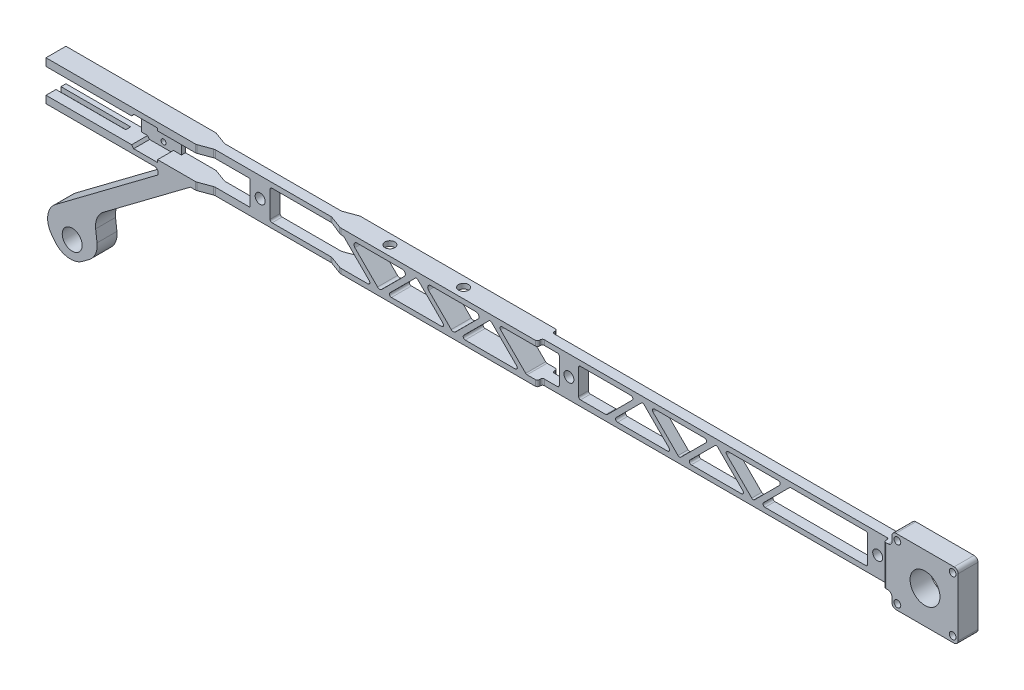
SolidWorks part; units mm, degrees
material "Magnesium Alloy"
ref_plane "Front Plane" through (0, 0, 0) normal (0, 0, 1) x (1, 0, 0)
ref_plane "Top Plane" through (0, 0, 0) normal (0, 1, 0) x (1, 0, 0)
ref_plane "Right Plane" through (0, 0, 0) normal (1, 0, 0) x (0, 0, -1)
sketch "Sketch1" plane through (0, 0, 0) normal (0, 0, 1) x (1, 0, 0)
  line L0 (2.54, 0) -> (568.96, 0)
  line L1 (571.5, 2.54) -> (571.5, 22.86)
  line L2 (568.96, 25.4) -> (2.54, 25.4)
  line L3 (0, 22.86) -> (0, 2.54)
  line L4 (0, 22.86) -> (0, 25.4)
  line L5 (0, 25.4) -> (2.54, 25.4)
  line L6 (2.54, 0) -> (0, 0)
  line L7 (0, 0) -> (0, 2.54)
  arc A1 (568.96, 25.4) -> (571.5, 22.86) centre (568.96, 22.86) cw
  arc A2 (571.5, 2.54) -> (568.96, 0) centre (568.96, 2.54) cw
  point P7 (0, 25.4)
  point P12 (571.5, 0)
  point P15 (0, 0)
  dimension "D1" = 571.5
  dimension "D2" = 25.4
extrude "Boss-Extrude1" add sketch "Sketch1" along normal blind 12.7
sketch "Sketch2" plane through (0, 0, 0) normal (0, 0, 1) x (1, 0, 0)
  line L0 (173.2461, 3.175) -> (205.2139, 3.175)
  line L1 (206.112, 5.343) -> (190.128, 21.327)
  line L2 (188.332, 21.327) -> (172.348, 5.343)
  line L3 (0, 0) -> (568.96, 0) construction
  line L4 (0, 25.4) -> (0, 0) construction
  arc A0 (188.332, 21.327) -> (190.128, 21.327) centre (189.23, 20.4289) cw
  arc A1 (206.112, 5.343) -> (205.2139, 3.175) centre (205.2139, 4.445) cw
  arc A2 (173.2461, 3.175) -> (172.348, 5.343) centre (173.2461, 4.445) cw
  point P9 (189.23, 22.225)
  point P12 (208.28, 3.175)
  point P15 (170.18, 3.175)
  dimension "D5" = 1.27
  dimension "D1" = 38.1
  dimension "D2" = 19.05
  dimension "D3" = 3.175
  dimension "D4" = 170.18
extrude "Cut-Extrude1" cut sketch "Sketch2" along normal blind 12.7
pattern_linear "LPattern1" count 7 spacing 46.99 along (1, 0, 0) skipping (1, 0), (2, 0), (3, 0) of "Cut-Extrude1"
sketch "Sketch3" plane through (0, 0, 0) normal (0, 0, 1) x (1, 0, 0)
  line L0 (149.7511, 22.225) -> (181.7189, 22.225)
  line L1 (182.617, 20.057) -> (166.633, 4.073)
  line L2 (164.837, 4.073) -> (148.853, 20.057)
  line L3 (568.96, 25.4) -> (0, 25.4) construction
  line L4 (0, 25.4) -> (0, 0) construction
  arc A0 (164.837, 4.073) -> (166.633, 4.073) centre (165.735, 4.9711) ccw
  arc A1 (182.617, 20.057) -> (181.7189, 22.225) centre (181.7189, 20.955) ccw
  arc A2 (149.7511, 22.225) -> (148.853, 20.057) centre (149.7511, 20.955) ccw
  point P9 (165.735, 3.175)
  point P12 (184.785, 22.225)
  point P15 (146.685, 22.225)
  dimension "D5" = 1.27
  dimension "D1" = 38.1
  dimension "D2" = 19.05
  dimension "D3" = 3.175
  dimension "D4" = 146.685
extrude "Cut-Extrude2" cut sketch "Sketch3" along normal blind 12.7
pattern_linear "LPattern2" count 8 spacing 46.99 along (1, 0, 0) skipping (1, 0), (2, 0) of "Cut-Extrude2"
ref_plane "Plane1" through (279.4, 0, 0) normal (1, 0, 0) x (0, 0, -1)
ref_plane "Plane2" through (330.2, 0, 0) normal (1, 0, 0) x (0, 0, -1)
sketch "Sketch37" plane through (0, 0, 12.7) normal (0, 0, 1) x (1, 0, 0)
  line L0 (198.2741, 22.225) -> (227.1759, 22.225)
  line L1 (228.523, 18.973) -> (214.072, 4.522)
  line L2 (211.378, 4.522) -> (196.927, 18.973)
  line L3 (0, 25.4) -> (0, 0) construction
  line L4 (568.96, 25.4) -> (0, 25.4) construction
  line L5 (206.112, 5.343) -> (190.128, 21.327) construction
  arc A0 (214.072, 4.522) -> (211.378, 4.522) centre (212.725, 5.8691) cw
  arc A1 (228.523, 18.973) -> (227.1759, 22.225) centre (227.1759, 20.32) ccw
  arc A2 (198.2741, 22.225) -> (196.927, 18.973) centre (198.2741, 20.32) ccw
  point P14 (231.775, 22.225)
  point P17 (193.675, 22.225)
  dimension "D4" = 1.905
  dimension "D1" = 38.1
  dimension "D2" = 193.675
  dimension "D3" = 3.175
extrude "Cut-Extrude13" cut sketch "Sketch37" against normal up to surface (12.7 mm away) up to face at (380.3287, 12.7, 0)
pattern_linear "LPattern5" count 2 spacing 46.99 along (1, 0, 0) of "Cut-Extrude13"
sketch "Sketch34" plane through (0, 0, 12.7) normal (0, 0, 1) x (1, 0, 0)
  line L0 (220.2361, 3.175) -> (252.2039, 3.175)
  line L1 (253.102, 5.343) -> (237.118, 21.327)
  line L2 (235.322, 21.327) -> (219.338, 5.343)
  line L3 (0, 0) -> (568.96, 0) construction
  line L4 (0, 25.4) -> (0, 0) construction
  line L6 (214.072, 4.522) -> (228.523, 18.973) construction
  arc A0 (235.322, 21.327) -> (237.118, 21.327) centre (236.22, 20.4289) cw
  arc A1 (253.102, 5.343) -> (252.2039, 3.175) centre (252.2039, 4.445) cw
  arc A2 (219.338, 5.343) -> (220.2361, 3.175) centre (220.2361, 4.445) ccw
  point P13 (255.27, 3.175)
  point P16 (217.17, 3.175)
  dimension "D4" = 1.27
  dimension "D1" = 38.1
  dimension "D2" = 3.175
  dimension "D3" = 217.17
extrude "Cut-Extrude10" cut sketch "Sketch34" against normal up to surface (12.7 mm away) up to face at (259.715, 15.297, 0)
pattern_linear "LPattern3" count 2 spacing 46.99 along (1, 0, 0) of "Cut-Extrude10"
sketch "Sketch19" plane through (0, 0, 0) normal (-1, 0, 0) x (0, 0, 1)
  line L0 (3.175, 1.5875) -> (6.35, 1.5875)
  line L1 (6.35, 1.5875) -> (6.35, 23.8125)
  line L2 (6.35, 23.8125) -> (3.175, 23.8125)
  line L3 (3.175, 23.8125) -> (3.175, 1.5875)
  line L4 (0, 25.4) -> (0, 0) construction
  line L5 (12.7, 0) -> (0, 0) construction
  dimension "D1" = 3.175
  dimension "D2" = 3.175
  dimension "D3" = 22.225
  dimension "D4" = 1.5875
extrude "Cut-Extrude4" cut sketch "Sketch19" against normal blind 44.45
sketch "Sketch18" plane through (0, 0, 12.7) normal (0, 0, 1) x (1, 0, 0)
  line L0 (0, 20.574) -> (50.8, 20.574)
  line L1 (0, 25.4) -> (0, 0) construction
  line L2 (50.8, 20.574) -> (50.8, 4.699)
  line L3 (50.8, 4.699) -> (0, 4.699)
  line L4 (0, 4.699) -> (0, 20.574)
  line L5 (568.96, 25.4) -> (0, 25.4) construction
  dimension "D1" = 50.8
  dimension "D2" = 15.875
  dimension "D3" = 4.826
extrude "Cut-Extrude3" cut sketch "Sketch18" against normal through all
sketch "Sketch20" plane through (0, 0, 12.7) normal (0, 0, 1) x (1, 0, 0)
  line L0 (50.8, 20.574) -> (54.61, 20.574)
  line L1 (54.61, 20.574) -> (55.88, 22.1615)
  line L2 (55.88, 22.1615) -> (71.12, 22.1615)
  line L3 (71.12, 22.1615) -> (71.12, 20.574)
  line L4 (71.12, 20.574) -> (127, 20.574)
  line L5 (127, 20.574) -> (127, 4.699)
  line L6 (127, 4.699) -> (71.12, 4.699)
  line L7 (71.12, 4.699) -> (71.12, 3.1115)
  line L8 (71.12, 3.1115) -> (55.88, 3.1115)
  line L9 (55.88, 3.1115) -> (54.61, 4.699)
  line L10 (54.61, 4.699) -> (50.8, 4.699)
  line L11 (50.8, 4.699) -> (50.8, 20.574)
  dimension "D1" = 3.81
  dimension "D2" = 1.5875
  dimension "D3" = 15.24
  dimension "D4" = 16.51
  dimension "D5" = 76.2
extrude "Cut-Extrude5" cut sketch "Sketch20" against normal blind 10.16
sketch "Sketch21" plane through (0, 0, 2.54) normal (0, 0, 1) x (1, 0, 0)
  line L0 (127, 20.574) -> (127, 4.699)
  line L1 (127, 4.699) -> (76.2, 4.699)
  line L2 (71.12, 4.699) -> (127, 4.699) construction
  line L3 (76.2, 4.699) -> (76.2, 20.574)
  line L4 (127, 20.574) -> (71.12, 20.574) construction
  line L5 (76.2, 20.574) -> (127, 20.574)
  dimension "D1" = 50.8
extrude "Cut-Extrude6" cut sketch "Sketch21" against normal through all
hole_wizard "1/8 (0.125) Diameter Hole1" positions "Sketch22" profile "Sketch23" hole size "1/8" standard "ANSI Inch" end condition through all
sketch "Sketch22" plane through (0, 0, 2.54) normal (0, 0, 1) x (1, 0, 0)
  line L0 (76.2, 20.574) -> (76.2, 4.699) construction
  line L1 (55.88, 3.1115) -> (71.12, 3.1115) construction
  line L2 (71.12, 22.1615) -> (55.88, 22.1615) construction
  point P0 (64.77, 18.9865)
  point P2 (64.77, 6.2865)
  dimension "D1" = 11.43
  dimension "D2" = 11.43
  dimension "D3" = 3.175
  dimension "D4" = 3.175
sketch "Sketch23" plane through (64.77, 18.9865, 2.54) normal (1, 0, 0) x (0, -1, 0)
  line L0 (0, 0) -> (0, 2.54)
  line L1 (0, 2.54) -> (1.5875, 2.54)
  line L2 (1.5875, 2.54) -> (1.5875, 0)
  line L5 (1.5875, 0) -> (0, 0)
  line L11 (0, -6.35) -> (0, 107.95) construction
  dimension "Thru Hole Dia." = 3.175
  dimension "Thru Hole Depth" = 2.54
ref_axis "Axis1" through (189.23, 21.6989, 12.7) along (0, 0, -1)
sketch "Sketch46" plane through (0, 0, 12.7) normal (0, 0, 1) x (1, 0, 0)
  line L2 (173.2461, 3.175) -> (140.97, 3.175)
  line L4 (139.7, 20.955) -> (139.7, 4.445)
  line L5 (127, 4.699) -> (127, 20.574) construction
  line L7 (173.2461, 3.175) -> (189.23, 21.6989)
  line L8 (181.7189, 22.225) -> (189.23, 21.6989)
  line L9 (181.7189, 22.225) -> (140.97, 22.225)
  arc A0 (139.7, 4.445) -> (140.97, 3.175) centre (140.97, 4.445) ccw
  arc A1 (140.97, 22.225) -> (139.7, 20.955) centre (140.97, 20.955) ccw
  dimension "D1" = 1.27
  dimension "D2" = 12.7
extrude "Cut-Extrude17" cut sketch "Sketch46" against normal up to surface (12.7 mm away) up to face at (66.3575, 18.9865, 0)
sketch "Sketch35" plane through (0, 0, 12.7) normal (0, 0, 1) x (1, 0, 0)
  line L13 (198.2741, 22.225) -> (214.072, 4.522)
  line L14 (214.072, 4.522) -> (212.725, 3.175)
  line L15 (212.725, 3.175) -> (140.97, 3.175)
  line L16 (198.2741, 22.225) -> (140.97, 22.225)
  line L17 (139.7, 20.955) -> (139.7, 4.445)
  line L18 (214.072, 4.522) -> (228.523, 18.973) construction
  line L19 (140.97, 3.175) -> (205.2139, 3.175) construction
  line L20 (127, 4.699) -> (127, 20.574) construction
  arc A5 (139.7, 4.445) -> (140.97, 3.175) centre (140.97, 4.445) ccw
  arc A6 (140.97, 22.225) -> (139.7, 20.955) centre (140.97, 20.955) ccw
  dimension "D2" = 1.27
  dimension "D1" = 12.7
extrude "Cut-Extrude11" [suppressed] cut sketch "Sketch35" against normal up to surface (12.7 mm away)
sketch "Sketch36" plane through (0, 0, 12.7) normal (0, 0, 1) x (1, 0, 0)
  line L0 (306.705, 3.7011) -> (322.834, 3.7011)
  line L1 (324.104, 4.9711) -> (324.104, 20.955)
  line L2 (322.834, 22.225) -> (322.6889, 22.225)
  line L3 (322.6889, 22.225) -> (306.705, 3.7011)
  line L4 (330.2, -6.985) -> (330.2, 6.985) construction
  arc A0 (305.807, 4.073) -> (307.603, 4.073) centre (306.705, 4.9711) ccw construction
  arc A1 (324.104, 4.9711) -> (322.834, 3.7011) centre (322.834, 4.9711) cw
  arc A2 (324.104, 20.955) -> (322.834, 22.225) centre (322.834, 20.955) ccw
  dimension "D2" = 1.27
  dimension "D1" = 6.096
extrude "Cut-Extrude12" cut sketch "Sketch36" against normal up to surface (12.7 mm away) up to face at (171.5874, 14.6574, 0)
mirror "Mirror1" about plane through (330.2, 0, 0) normal (1, 0, 0) of "Cut-Extrude12"
sketch "Sketch45" plane through (0, 0, 12.7) normal (0, 0, 1) x (1, 0, 0)
  line L5 (487.1539, 3.175) -> (519.43, 3.175)
  line L7 (487.1539, 3.175) -> (470.272, 21.327)
  line L8 (470.272, 21.327) -> (470.798, 21.853)
  line L9 (471.6961, 22.225) -> (510.6489, 22.225)
  line L10 (470.272, 21.327) -> (454.288, 5.343) construction
  line L13 (520.7, 4.445) -> (520.7, 20.955)
  line L14 (519.43, 22.225) -> (510.6489, 22.225)
  line L15 (330.2, -6.985) -> (330.2, 6.985) construction
  arc A3 (471.6961, 22.225) -> (470.798, 21.853) centre (471.6961, 20.955) ccw
  arc A4 (519.43, 22.225) -> (520.7, 20.955) centre (519.43, 20.955) cw
  arc A5 (520.7, 4.445) -> (519.43, 3.175) centre (519.43, 4.445) cw
  dimension "D1" = 190.5
  dimension "D3" = 1.27
  dimension "D2" = 1.27
sketch "Sketch8" plane through (0, 0, 0) normal (0, 0, 1) x (1, 0, 0)
  line L0 (92.075, 0) -> (-9.525, -76.2)
  line L1 (0, 0) -> (568.96, 0) construction
  line L2 (-9.525, -76.2) -> (-15.24, -68.58)
  line L3 (-15.24, -68.58) -> (76.2, 0)
  line L4 (76.2, 0) -> (92.075, 0)
  line L6 (0, 25.4) -> (0, 20.574) construction
  dimension "D1" = 76.2
  dimension "D2" = 101.6
  dimension "D3" = 9.525
  dimension "D4" = 76.2
extrude "Boss-Extrude3" add sketch "Sketch8" along normal blind 12.7
sketch "Sketch13" plane through (0, 0, 0) normal (0, 0, 1) x (1, 0, 0)
  line L1 (76.2, 0) -> (-15.24, -68.58) construction
  line L5 (69.85, 0) -> (76.2, 0)
  line L6 (76.2, 0) -> (71.12, -3.81)
  arc A0 (69.85, 0) -> (71.12, -3.81) centre (69.0094, -2.3969) cw
  point P10 (76.2, 0)
  dimension "D1" = 2.54
  dimension "D2" = 6.35
extrude "Boss-Extrude4" add sketch "Sketch13" along normal blind 12.7
sketch "Sketch29" plane through (0, 0, 12.7) normal (0, 0, 1) x (1, 0, 0)
  line L0 (-9.525, -76.2) -> (1.651, -67.818)
  line L1 (-9.525, -76.2) -> (92.075, 0) construction
  line L2 (1.651, -67.818) -> (-0.254, -65.278)
  line L3 (-0.254, -65.278) -> (-11.43, -73.66)
  line L4 (-15.24, -68.58) -> (-9.525, -76.2) construction
  line L5 (-11.43, -73.66) -> (-9.525, -76.2)
  line L6 (71.12, -3.81) -> (-15.24, -68.58) construction
  dimension "D1" = 13.97
  dimension "D2" = 6.35
extrude "Cut-Extrude7" cut sketch "Sketch29" against normal up to surface (12.7 mm away) up to face at (172.8524, -1.4355, 0)
sketch "Sketch30" plane through (0, 0, 0) normal (0, 0, -1) x (-1, 0, 0)
  line L0 (-1.651, -67.818) -> (-92.075, 0) construction
  line L1 (-1.651, -67.818) -> (-13.081, -83.058)
  line L2 (-13.081, -83.058) -> (-33.401, -67.818)
  line L3 (-33.401, -67.818) -> (-30.7698, -45.9789)
  line L4 (-30.7698, -45.9789) -> (-1.651, -67.818)
  circle A0 centre (-16.6878, -66.7004) radius 6.35
  dimension "D1" = 8.128
  dimension "D2" = 90
  dimension "D3" = 12.7
  dimension "D4" = 25.4
  dimension "D5" = 60
  dimension "D6" = 19.05
extrude "Boss-Extrude5" add sketch "Sketch30" against normal blind 12.7
sketch "Sketch31" plane through (0, 0, 0) normal (0, 0, -1) x (-1, 0, 0)
  line L0 (0.254, -65.278) -> (4.064, -60.198)
  line L1 (-71.12, -3.81) -> (15.24, -68.58) construction
  line L2 (4.064, -60.198) -> (15.24, -68.58)
  line L3 (15.24, -68.58) -> (11.43, -73.66)
  line L4 (11.43, -73.66) -> (0.254, -65.278)
  dimension "D1" = 90
extrude "Cut-Extrude8" cut sketch "Sketch31" against normal blind 18.796
fillet "Fillet1" radius 12.7 4 edges at (30.7698, -45.9789, 6.35) (33.401, -67.818, 6.35) (-4.064, -60.198, 6.35) (13.081, -83.058, 6.35)
hole_wizard "1/4 (0.25) Diameter Hole2" positions "Sketch24" profile "Sketch25" hole size "1/4" standard "ANSI Inch" end condition through all
sketch "Sketch24" plane through (0, 0, 12.7) normal (0, 0, 1) x (1, 0, 0)
  line L0 (568.96, 25.4) -> (0, 25.4) construction
  line L2 (0, 25.4) -> (0, 20.574) construction
  point P0 (133.35, 12.7)
  point P2 (330.2, 12.7)
  point P4 (527.05, 12.7)
  dimension "D1" = 12.7
  dimension "D2" = 133.35
  dimension "D3" = 12.7
  dimension "D4" = 196.85
  dimension "D5" = 12.7
  dimension "D6" = 393.7
sketch "Sketch25" plane through (133.35, 12.7, 12.7) normal (1, 0, 0) x (0, -1, 0)
  line L0 (0, 0) -> (0, 12.7)
  line L1 (0, 12.7) -> (3.175, 12.7)
  line L2 (3.175, 12.7) -> (3.175, 0)
  line L5 (3.175, 0) -> (0, 0)
  line L11 (0, -6.35) -> (0, 107.95) construction
  dimension "Thru Hole Dia." = 6.35
  dimension "Thru Hole Depth" = 12.7
hole_wizard "1/4 (0.25) Diameter Hole3" positions "Sketch26" profile "Sketch28" hole size "1/4" standard "ANSI Inch"
sketch "Sketch26" plane through (0, 25.4, 0) normal (0, 1, 0) x (1, 0, 0)
  line L0 (568.96, 0) -> (0, 0) construction
  line L2 (568.96, -12.7) -> (0, -12.7) construction
  line L6 (227.1759, 0) -> (227.1759, -12.7) construction
  line L7 (274.1659, 0) -> (274.1659, -12.7) construction
  point P2 (212.8884, -6.35)
  point P7 (259.8784, -6.35)
  dimension "D1" = 6.35
  dimension "D2" = 6.35
  dimension "D3" = 14.2875
  dimension "D4" = 14.2875
sketch "Sketch28" plane through (212.8884, 25.4, 6.35) normal (1, 0, 0) x (0, 0, 1)
  line L0 (0, 0) -> (0, 5.0827)
  line L1 (0, 5.0827) -> (3.175, 3.175)
  line L2 (3.175, 3.175) -> (3.175, 0)
  line L5 (3.175, 0) -> (0, 0)
  line L10 (0, 5.0827) -> (-3.175, 3.175) construction
  line L11 (0, -6.35) -> (0, 107.95) construction
  dimension "Hole Dia." = 6.35
  dimension "Hole Depth" = 3.175
  dimension "Drill Angle" = 118
hole_wizard "1/4 (0.25) Diameter Hole1" positions "Sketch14" profile "Sketch15" hole size "1/4" standard "ANSI Inch" end condition through all
sketch "Sketch14" plane through (0, 0, 12.7) normal (0, 0, 1) x (1, 0, 0)
  line L0 (571.5, 2.54) -> (571.5, 22.86) construction
  line L1 (568.96, 25.4) -> (0, 25.4) construction
  point P0 (560.3875, 12.7)
  dimension "D1" = 11.1125
  dimension "D2" = 12.7
sketch "Sketch15" plane through (560.3875, 12.7, 12.7) normal (1, 0, 0) x (0, -1, 0)
  line L0 (0, 0) -> (0, 12.7)
  line L1 (0, 12.7) -> (3.175, 12.7)
  line L2 (3.175, 12.7) -> (3.175, 0)
  line L5 (3.175, 0) -> (0, 0)
  line L11 (0, -6.35) -> (0, 107.95) construction
  dimension "Thru Hole Dia." = 6.35
  dimension "Thru Hole Depth" = 12.7
sketch "Sketch32" plane through (0, 0, 0) normal (0, 0, -1) x (-1, 0, 0)
  line L1 (-581.4695, 12.7) -> (-581.4695, 33.782)
  line L2 (-581.4695, 33.782) -> (-539.3055, 33.782)
  line L3 (-539.3055, 33.782) -> (-539.3055, 25.4)
  line L4 (-568.96, 25.4) -> (0, 25.4) construction
  line L5 (-539.3055, 25.4) -> (-539.3055, 0)
  line L6 (-92.075, 0) -> (-568.96, 0) construction
  line L7 (-581.4695, 12.7) -> (-581.4695, -8.382)
  line L8 (-581.4695, -8.382) -> (-539.3055, -8.382)
  line L9 (-539.3055, -8.382) -> (-539.3055, 0)
  line L11 (-581.4695, 12.7) -> (-560.3875, 12.7) construction
  circle A0 centre (-560.3875, 12.7) radius 3.175
  dimension "D6" = 6.35
  dimension "D1" = 21.082
  dimension "D2" = 21.082
  dimension "D4" = 42.164
  dimension "D5" = 21.082
extrude "Boss-Extrude6" add sketch "Sketch32" against normal blind 12.7
sketch "Sketch33" plane through (0, 0, 12.7) normal (0, 0, 1) x (1, 0, 0)
  circle A0 centre (560.3875, 12.7) radius 9.525
  circle A1 centre (560.3875, 12.7) radius 24.7523
  circle A2 centre (578.0051, 30.0867) radius 2.159
  circle A3 centre (578.0051, -4.6867) radius 2.159
  circle A4 centre (542.7699, -4.6867) radius 2.159
  circle A5 centre (542.7699, 30.0867) radius 2.159
  dimension "D1" = 19.05
  dimension "D2" = 49.5046
  dimension "D3" = 4.318
  dimension "D4" = 4.318
  dimension "D5" = 4.318
  dimension "D6" = 4.318
extrude "Cut-Extrude9" cut sketch "Sketch33" against normal blind 12.7 contours A0 | A1 A2 | A1 A2 | A1 A5 | A1 A5 | A1 A3 | A1 A3 | A1 A4 | A1 A4 region at (560.3875, 12.7, 12.7) region at (577.341, 29.4313, 12.7) region at (578.6451, 30.7182, 12.7) region at (578.6451, -5.3182, 12.7) region at (577.341, -4.0313, 12.7) region at (543.434, 29.4313, 12.7) region at (542.1299, 30.7182, 12.7) region at (542.1299, -5.3182, 12.7) region at (543.434, -4.0313, 12.7)
fillet "Fillet2" radius 2.54 6 edges at (581.4695, -8.382, 6.35) (539.3055, 0, 6.35) (539.3055, -8.382, 6.35) (581.4695, 33.782, 6.35) (539.3055, 33.782, 6.35) (539.3055, 25.4, 6.35)
extrude "Cut-Extrude16" cut sketch "Sketch45" against normal up to surface (12.7 mm away) up to face at (544.9289, -4.6867, 0)
sketch "Sketch38" plane through (0, 25.4, 0) normal (0, 1, 0) x (1, 0, 0)
  line L0 (339.9918, -0.1655) -> (345.8082, -2.3745)
  line L2 (346.71, -2.54) -> (510.54, -2.54)
  line L3 (511.4418, -2.3745) -> (517.2582, -0.1655)
  line L6 (339.09, 0) -> (518.16, 0)
  line L7 (330.2, -6.985) -> (330.2, 6.985) construction
  arc A0 (511.4418, -2.3745) -> (510.54, -2.54) centre (510.54, 0) cw
  arc A1 (346.71, -2.54) -> (345.8082, -2.3745) centre (346.71, 0) cw
  arc A2 (518.16, 0) -> (517.2582, -0.1655) centre (518.16, -2.54) ccw
  arc A3 (339.9918, -0.1655) -> (339.09, 0) centre (339.09, -2.54) ccw
  point P10 (511.0061, -2.54)
  point P13 (346.2439, -2.54)
  dimension "D5" = 2.54
  dimension "D6" = 2.54
  dimension "D1" = 179.07
  dimension "D2" = 163.83
  dimension "D3" = 2.54
  dimension "D4" = 8.89
extrude "Cut-Extrude14" [suppressed] cut sketch "Sketch38" against normal up to surface (25.4 mm away)
ref_plane "Plane3" through (0, 0, 6.35) normal (0, 0, 1) x (1, 0, 0)
sketch "Sketch40" plane through (0, 25.4, 0) normal (0, 1, 0) x (1, 0, 0)
  line L0 (187.96, 0) -> (95.25, 0)
  line L2 (187.082, -0.1566) -> (179.313, -3.0184)
  line L3 (178.435, -3.175) -> (104.775, -3.175)
  line L4 (103.897, -3.0184) -> (96.128, -0.1566)
  line L5 (279.4, -6.985) -> (279.4, 6.985) construction
  arc A0 (95.25, 0) -> (96.128, -0.1566) centre (95.25, -2.54) cw
  arc A1 (187.96, 0) -> (187.082, -0.1566) centre (187.96, -2.54) ccw
  arc A2 (103.897, -3.0184) -> (104.775, -3.175) centre (104.775, -0.635) ccw
  arc A3 (179.313, -3.0184) -> (178.435, -3.175) centre (178.435, -0.635) cw
  dimension "D1" = 2.54
  dimension "D2" = 92.71
  dimension "D3" = 91.44
  dimension "D4" = 73.66
  dimension "D5" = 3.175
extrude "Cut-Extrude15" cut sketch "Sketch40" against normal up to surface (25.4 mm away)
sketch "Sketch47" plane through (0, 0, 0) normal (0, -1, 0) x (1, 0, 0)
  line L0 (534.2255, 11.43) -> (534.2255, 10.795)
  line L1 (92.075, 12.7) -> (536.7655, 12.7) construction
  line L2 (532.9555, 9.525) -> (314.5155, 9.525)
  line L3 (313.2455, 10.795) -> (313.2455, 11.43)
  line L4 (311.9755, 12.7) -> (534.2255, 12.7)
  line L5 (536.7655, 0) -> (536.7655, 12.7) construction
  line L6 (534.2255, 12.7) -> (535.4955, 12.7)
  arc A0 (534.2255, 10.795) -> (532.9555, 9.525) centre (532.9555, 10.795) cw
  arc A1 (534.2255, 11.43) -> (535.4955, 12.7) centre (535.4955, 11.43) cw
  arc A2 (314.5155, 9.525) -> (313.2455, 10.795) centre (314.5155, 10.795) cw
  arc A3 (313.2455, 11.43) -> (311.9755, 12.7) centre (311.9755, 11.43) ccw
  point P14 (534.2255, 9.525)
  dimension "D4" = 1.27
  dimension "D1" = 3.175
  dimension "D2" = 222.25
  dimension "D3" = 2.54
extrude "Cut-Extrude18" cut sketch "Sketch47" against normal up to surface (25.4 mm away)
mirror "Mirror2" about plane through (0, 0, 6.35) normal (0, 0, 1) of "Cut-Extrude18", "Cut-Extrude15"
